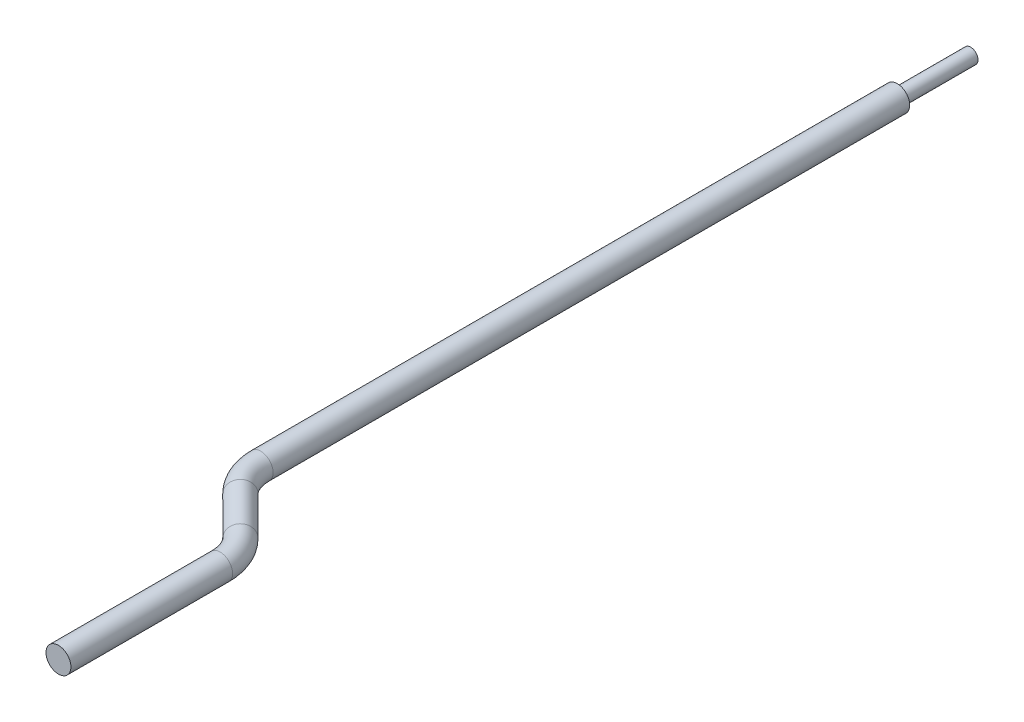
SolidWorks part; units mm, degrees
note: '?' marks a value the reader was unsure of.
ref_plane "Front" through (0, 0, 0) normal (0, 0, 1) x (1, 0, 0)
ref_plane "Top" through (0, 0, 0) normal (0, 1, 0) x (1, 0, 0)
ref_plane "Right" through (0, 0, 0) normal (1, 0, 0) x (0, 0, -1)
sketch "Sketch1" plane through (0, 0, 0) normal (0, 0, 1) x (1, 0, 0)
  circle A0 centre (0, 0) radius 0.6477
  dimension "D1" = 1.2954
extrude "Boss-Extrude1" add sketch "Sketch1" along normal blind 35.56
ref_axis "Axis1" through (0, 0, 50) along (0, 0, -1)?
sketch "Sketch2" plane through (0, 0, 0) normal (0, 1, 0) x (1, 0, 0)
  line L0 (3.4798, -50.8) -> (3.4798, -42.414)
  line L1 (0, -35.56) -> (0, -36.83)
  line L3 (-0.6477, -35.56) -> (0.6477, -35.56) construction
  line L4 (0.7439, -38.6261) -> (2.7359, -40.618)
  arc A0 (2.7359, -40.618) -> (3.4798, -42.414) centre (0.9398, -42.414) cw
  arc A1 (0, -36.83) -> (0.7439, -38.6261) centre (2.54, -36.83) ccw
  dimension "D4" = 2.54
  dimension "D1" = 15.24
  dimension "D2" = 3.4798
  dimension "D3" = 45
  dimension "D5" = 1.27
sketch "Sketch3" plane through (0, 0, 35.56) normal (0, 0, 1) x (1, 0, 0)
  circle A0 centre (0, 0) radius 0.6477
  circle A1 centre (0, 0) radius 0.6477 construction
sweep "Sweep1" add profiles "Sketch3" path "Sketch2"
sketch "Sketch4" plane through (0, 0, 0) normal (0, 0, 1) x (1, 0, 0)
  circle A0 centre (0, 0) radius 0.381
  circle A1 centre (0, 0) radius 0.6477
  circle A3 centre (0, 0) radius 0.6477 construction
  circle M4 centre (0, 0) radius 0.6477
  dimension "D1" = 0.762
extrude "Cut-Extrude2" cut sketch "Sketch4" along normal blind 3.81 contours A0 M4
ref_point "Point1"
ref_point "Point2"
